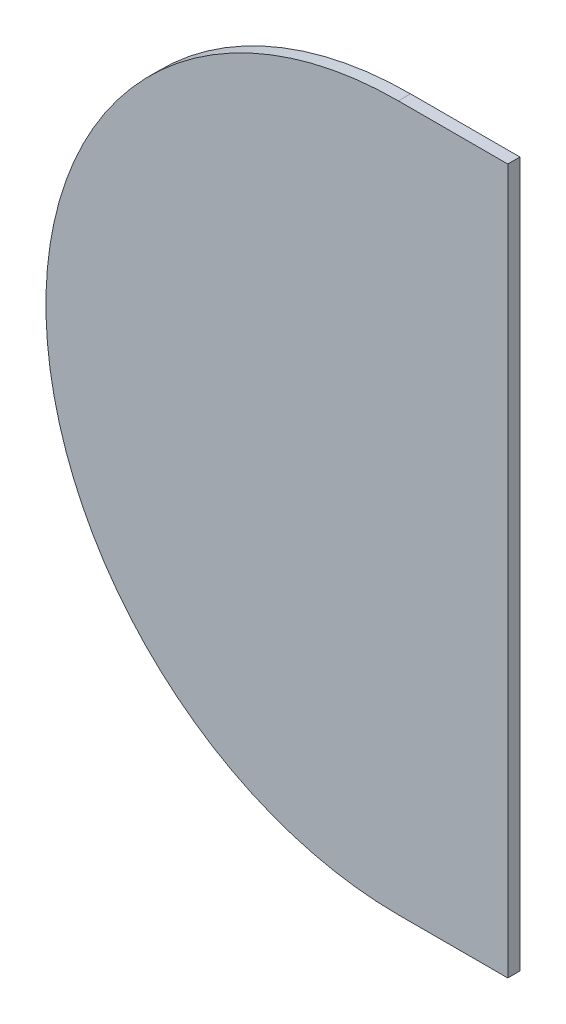
SolidWorks part; units mm, degrees
ref_plane "Front Plane" through (0, 0, 0) normal (0, 0, 1) x (1, 0, 0)
ref_plane "Top Plane" through (0, 0, 0) normal (0, 1, 0) x (1, 0, 0)
ref_plane "Right Plane" through (0, 0, 0) normal (1, 0, 0) x (0, 0, -1)
sketch "Sketch1" plane through (0, 0, 0) normal (0, 0, 1) x (1, 0, 0)
  line L1 (0, 0) -> (270, 0)
  line L2 (0, 0) -> (0, 1740) construction
  line L3 (0, 1740) -> (270, 1740)
  line L4 (270, 0) -> (270, 1740)
  arc A0 (0, 1740) -> (0, 0) centre (0, 870) ccw
  dimension "D1" = 270
  dimension "D2" = 1740
extrude "Boss-Extrude1" add sketch "Sketch1" along normal blind 30
